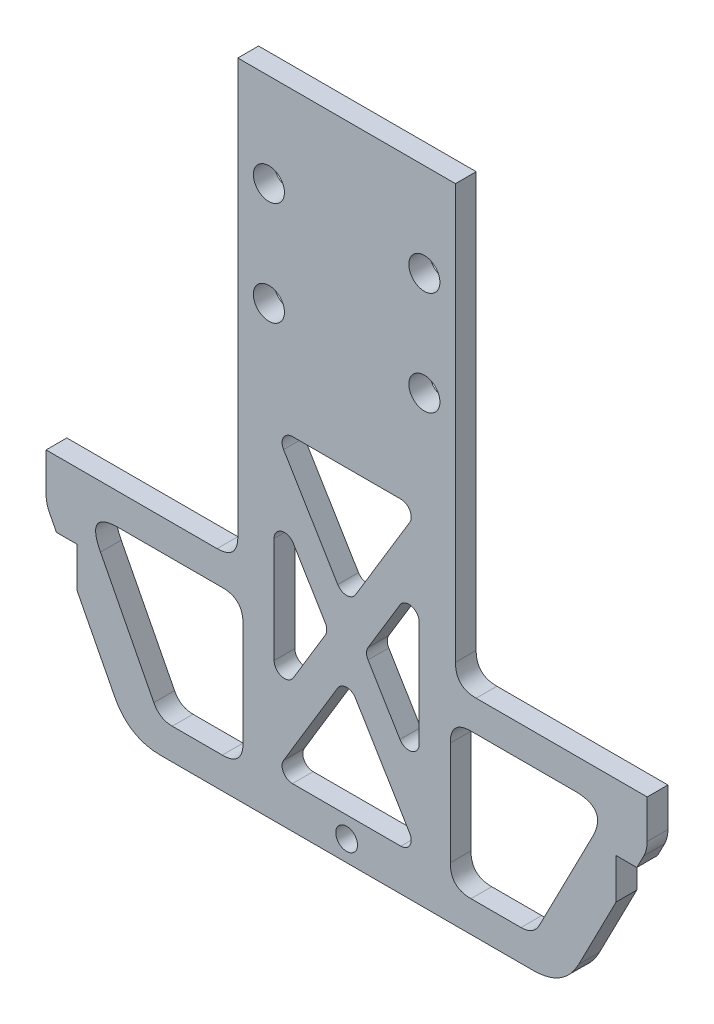
SolidWorks part; units mm, degrees
material "Thornel Mat VMA"
ref_plane "前视基准面" through (0, 0, 0) normal (0, 0, 1) x (1, 0, 0)
ref_plane "上视基准面" through (0, 0, 0) normal (0, 1, 0) x (1, 0, 0)
ref_plane "右视基准面" through (0, 0, 0) normal (1, 0, 0) x (0, 0, -1)
sketch "草图1" plane through (0, 0, 0) normal (0, 0, 1) x (1, 0, 0)
  line L0 (0, 36.2949) -> (0, -36.0138) construction
  line L1 (-40.9048, 0) -> (52.0636, 0) construction
  line L2 (10.5, -14) -> (10.5, 14) construction
  line L3 (-10.5, 14) -> (10.5, 14)
  line L4 (-10.5, 14) -> (-10.5, -14)
  line L5 (-10.5, -14) -> (10.5, -14)
  line L6 (34.5, 4) -> (34.5, -4)
  line L7 (10.5, 14) -> (10.5, 4)
  line L8 (10.5, 4) -> (34.5, 4)
  line L9 (10.5, -14) -> (10.5, -4)
  line L10 (10.5, -4) -> (34.5, -4)
  circle A0 centre (-7.5, 5) radius 1.5
  circle A1 centre (7.5, 5) radius 1.5
  circle A2 centre (-7.5, -5) radius 1.5
  circle A3 centre (7.5, -5) radius 1.5
  circle A4 centre (16.5, 0) radius 1.5
  circle A5 centre (31.5, 0) radius 1.5
  dimension "D1" = 3
  dimension "D2" = 10
  dimension "D3" = 15
  dimension "D4" = 3
  dimension "D5" = 9
  dimension "D8" = 3
  dimension "D9" = 15
  dimension "D10" = 3
  dimension "D11" = 6
  dimension "D6" = 24
  dimension "D7" = 3
  dimension "D12" = 4
  dimension "D13" = 4
extrude "凸台-拉伸1" add sketch "草图1" along normal blind 2
fillet "圆角1" radius 2 2 edges at (10.5, -4, 1) (10.5, 4, 1)
sketch "草图3" plane through (0, 0, 2) normal (0, 0, 1) x (1, 0, 0)
  line L1 (10.5, 14) -> (35.6387, 14)
  line L2 (10.5, 14) -> (10.5, -15.7039)
  line L3 (10.5, -15.7039) -> (35.6387, -15.7039)
  line L4 (35.6387, 14) -> (35.6387, -15.7039)
extrude "切除-拉伸1" cut sketch "草图3" against normal through all
sketch "草图4" plane through (0, 0, 2) normal (0, 0, 1) x (1, 0, 0)
  line L0 (10.5, -14) -> (10.5, 14) construction
  line L1 (-10.5, -48) -> (10.5, -48)
  line L2 (-10.5, -48) -> (-10.5, -14)
  line L3 (-10.5, -14) -> (10.5, -14)
  line L4 (10.5, -48) -> (10.5, -14)
  line L5 (-10.5, -14) -> (10.5, -14) construction
  line L6 (0, 0) -> (0, -48) construction
  line L8 (-7, -15) -> (7, -15)
  line L9 (-7, -15) -> (-7, -44)
  line L10 (-7, -44) -> (7, -44)
  line L11 (7, -15) -> (7, -44)
  dimension "D1" = 34
  dimension "D2" = 1
  dimension "D3" = 3.5
  dimension "D4" = 4
extrude "凸台-拉伸2" add sketch "草图4" against normal up to surface (2 mm away) up to face at (0, 0, 0)
sketch "草图5" plane through (0, 0, 2) normal (0, 0, 1) x (1, 0, 0)
  line L0 (-7, -15) -> (0, -26.5973)
  line L1 (7, -44) -> (7, -15) construction
  line L2 (7, -38.1945) -> (7, -44)
  line L3 (7, -44) -> (0, -32.4027)
  line L4 (-7, -15) -> (-7, -44) construction
  line L5 (-7, -20.8055) -> (-7, -15)
  line L6 (7, -15) -> (0, -26.5973)
  line L7 (-7, -38.1945) -> (-7, -44)
  line L8 (-7, -44) -> (0, -32.4027)
  line L9 (7, -20.8055) -> (7, -15)
  line L10 (1.7521, -29.5) -> (7, -38.1945)
  line L11 (1.7521, -29.5) -> (7, -20.8055)
  line L12 (-1.7521, -29.5) -> (-7, -38.1945)
  line L13 (-1.7521, -29.5) -> (-7, -20.8055)
  dimension "D1" = 3
extrude "凸台-拉伸3" add sketch "草图5" against normal up to surface (2 mm away) up to face at (0, -17, 0)
fillet "圆角2" radius 1 12 edges at (7, -20.8055, 1) (1.7521, -29.5, 1) (7, -38.1945, 1) (7, -44, 1) (0, -32.4027, 1) (-7, -44, 1) (-7, -38.1945, 1) (-1.7521, -29.5, 1) (-7, -20.8055, 1) (0, -26.5973, 1) (7, -15, 1) (-7, -15, 1)
sketch "草图6" plane through (0, 0, 2) normal (0, 0, 1) x (1, 0, 0)
  line L0 (0, -48) -> (0, 0) construction
  line L1 (-10.5, -48) -> (10.5, -48) construction
  line L2 (-5.2284, -44) -> (5.2284, -44) construction
  circle A0 centre (0, -46) radius 1.05
  dimension "D1" = 2.1
  dimension "D2" = 2
extrude "切除-拉伸2" cut sketch "草图6" against normal through all
sketch "草图7" plane through (0, 0, 2) normal (0, 0, 1) x (1, 0, 0)
  line L0 (10.5, -48) -> (10.5, 14) construction
  line L1 (10.5, -31) -> (29, -31)
  line L2 (10.5, -31) -> (10.5, -34)
  line L3 (10.5, -48) -> (29, -48)
  line L4 (29, -31) -> (29, -48)
  line L5 (-10.5, 14) -> (-10.5, -48) construction
  line L6 (-10.5, -31) -> (-29, -31)
  line L7 (-10.5, -31) -> (-10.5, -34)
  line L8 (-10.5, -48) -> (-29, -48)
  line L9 (-29, -31) -> (-29, -48)
  line L10 (0, 0) -> (0, -60.1052) construction
  line L12 (-10.5, -45) -> (-10.5, -48)
  line L13 (-26, -34) -> (-10.5, -34)
  line L14 (-26, -34) -> (-26, -45)
  line L15 (-26, -45) -> (-10.5, -45)
  line L17 (26, -34) -> (10.5, -34)
  line L18 (26, -34) -> (26, -45)
  line L19 (26, -45) -> (10.5, -45)
  line L21 (10.5, -45) -> (10.5, -48)
  dimension "D1" = 18.5
  dimension "D3" = 17
  dimension "D4" = 3
  dimension "D5" = 3
  dimension "D6" = 3
extrude "凸台-拉伸4" add sketch "草图7" against normal up to surface (2 mm away) up to face at (1.05, -46, 0)
sketch "草图8" plane through (0, -31, 0) normal (0, 1, 0) x (1, 0, 0)
  line L4 (29, 0) -> (10.5, 0)
  line L5 (10.5, 0) -> (10.5, -2)
  line L6 (10.5, -2) -> (29, -2)
  line L7 (29, -2) -> (29, 0)
  line L8 (29, 0) -> (10.5, 0)
  line L9 (10.5, 0) -> (10.5, -2)
  line L10 (10.5, -2) -> (29, -2)
  line L11 (29, -2) -> (29, 0)
  line L12 (-10.5, 0) -> (-29, 0)
  line L13 (-29, 0) -> (-29, -2)
  line L14 (-29, -2) -> (-10.5, -2)
  line L15 (-10.5, -2) -> (-10.5, 0)
  line L16 (-10.5, 0) -> (-29, 0)
  line L17 (-29, 0) -> (-29, -2)
  line L18 (-29, -2) -> (-10.5, -2)
  line L19 (-10.5, -2) -> (-10.5, 0)
  dimension "D1" = 0
  dimension "D2" = 0
extrude "凸台-拉伸5" add sketch "草图8" along normal blind 3
sketch "草图9" plane through (0, 0, 2) normal (0, 0, 1) x (1, 0, 0)
  line L1 (-26, -34) -> (-10.5, -34)
  line L2 (-26, -34) -> (-26, -45)
  line L3 (-26, -45) -> (-10.5, -45)
  line L4 (-10.5, -34) -> (-10.5, -45)
  line L5 (-26, -34) -> (-10.5, -45) construction
  line L6 (-26, -45) -> (-10.5, -34) construction
  line L7 (10.5, -34) -> (26, -34)
  line L8 (10.5, -34) -> (10.5, -45)
  line L9 (10.5, -45) -> (26, -45)
  line L10 (26, -34) -> (26, -45)
  line L11 (10.5, -34) -> (26, -45) construction
  line L12 (10.5, -45) -> (26, -34) construction
  point P4 (-18.25, -39.5)
  point P11 (18.25, -39.5)
extrude "凸台-拉伸6" add sketch "草图9" against normal up to surface (2 mm away) up to face at (0, -22.5, 0)
sketch "草图10" plane through (0, 0, 2) normal (0, 0, 1) x (1, 0, 0)
  line L0 (-29, -32.45) -> (-21, -48)
  line L1 (-29, -28) -> (-29, -48) construction
  line L2 (-29, -48) -> (29, -48) construction
  line L3 (-21, -48) -> (-29, -48)
  line L4 (-29, -48) -> (-29, -32.45)
  line L5 (29, -32.45) -> (21, -48)
  line L6 (29, -48) -> (29, -28) construction
  line L7 (21, -48) -> (29, -48)
  line L8 (29, -48) -> (29, -32.45)
  line L9 (-29, -28) -> (-10.5, -28) construction
  line L10 (10.5, -28) -> (29, -28) construction
  dimension "D1" = 4.45
  dimension "D2" = 4.45
  dimension "D3" = 8
  dimension "D4" = 8
extrude "切除-拉伸3" cut sketch "草图10" against normal blind 3
fillet "圆角3" radius 5 2 edges at (21, -48, 1) (-21, -48, 1) conic rho 0.5
fillet "圆角4" radius 3 2 edges at (29, -32.45, 1) (-29, -32.45, 1) conic rho 0.5
sketch "草图11" plane through (0, 0, 2) normal (0, 0, 1) x (1, 0, 0)
  line L0 (0, 0) -> (0, -8.7604) construction
  line L1 (-26, -38.2812) -> (-26, -34.3938)
  line L2 (-22.3956, -45.2874) -> (-28.6677, -33.096) construction
  line L4 (-28, -34.3938) -> (-28, -38.2812)
  line L5 (-28, -38.2812) -> (-26, -38.2812)
  line L6 (-29, -28) -> (-29, -31.7235) construction
  line L7 (-28, -34.3938) -> (-26, -34.3938)
  line L8 (28, -34.3938) -> (26, -34.3938)
  line L9 (28, -38.2812) -> (26, -38.2812)
  line L10 (28, -34.3938) -> (28, -38.2812)
  line L11 (26, -38.2812) -> (26, -34.3938)
  dimension "D1" = 3
  dimension "D2" = 2
extrude "切除-拉伸4" cut sketch "草图11" against normal blind 3
sketch "草图12" plane through (0, 0, 2) normal (0, 0, 1) x (1, 0, 0)
  line L0 (-25.2477, -31) -> (-18.0451, -45)
  line L1 (-18.0451, -45) -> (-10, -45)
  line L2 (-10, -45) -> (-10, -31)
  line L3 (-25.2477, -31) -> (-10, -31)
  line L4 (-29, -28) -> (-10.5, -28) construction
  line L6 (-7, -24.3974) -> (-7, -34.6026) construction
  line L7 (-17.9495, -48) -> (17.9495, -48) construction
  line L8 (-22.3956, -45.2874) -> (-26, -38.2812) construction
  line L9 (0, -50.7906) -> (0, -41.2163) construction
  line L10 (25.2477, -31) -> (10, -31)
  line L11 (10, -45) -> (10, -31)
  line L12 (18.0451, -45) -> (10, -45)
  line L13 (25.2477, -31) -> (18.0451, -45)
  dimension "D1" = 3
  dimension "D2" = 4
  dimension "D3" = 3
  dimension "D4" = 3
extrude "切除-拉伸5" cut sketch "草图12" against normal blind 3
fillet "圆角5" radius 2 10 edges at (10.5, -28, 1) (25.2477, -31, 1) (18.0451, -45, 1) (10, -45, 1) (10, -31, 1) (-10.5, -28, 1) (-18.0451, -45, 1) (-10, -45, 1) (-10, -31, 1) (-25.2477, -31, 1) conic rho 0.5
